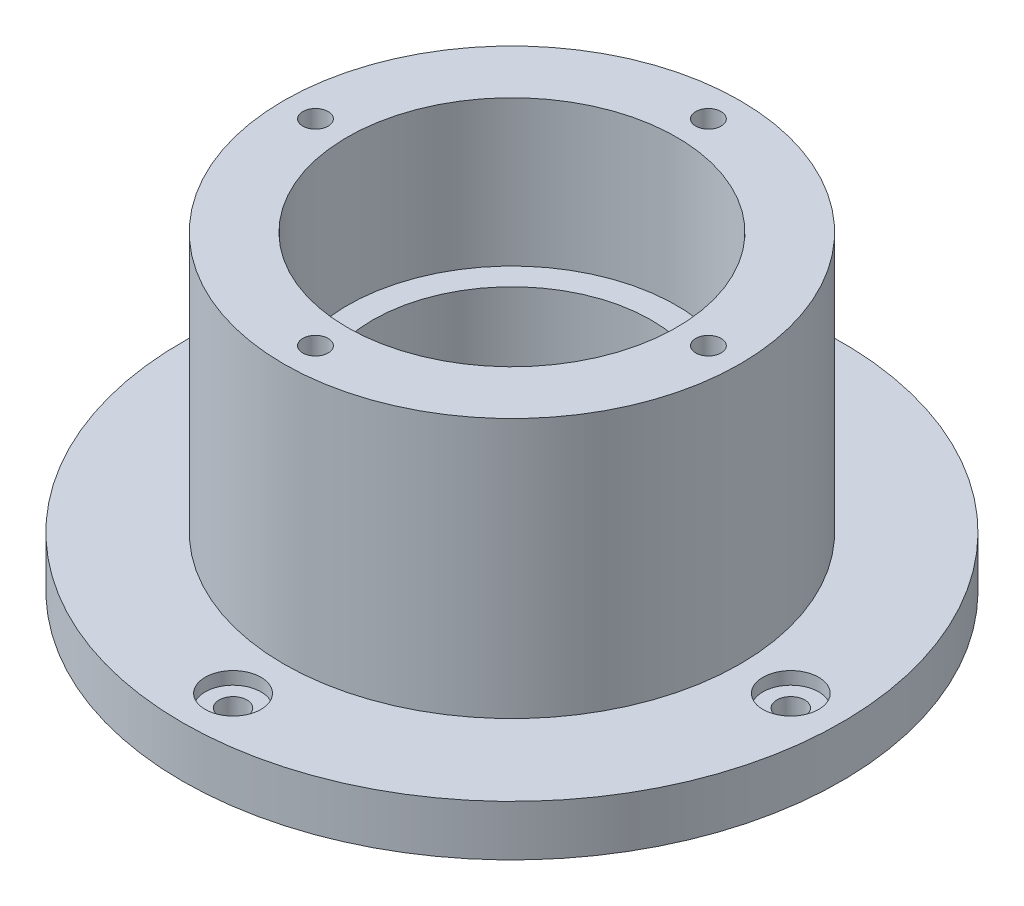
SolidWorks part; units mm, degrees
material "ABS"
ref_plane "Спереди" through (0, 0, 0) normal (0, 0, 1) x (1, 0, 0)
ref_plane "Сверху" through (0, 0, 0) normal (0, 1, 0) x (1, 0, 0)
ref_plane "Справа" through (0, 0, 0) normal (1, 0, 0) x (0, 0, -1)
sketch "Эскиз1" plane through (0, 0, 0) normal (0, 1, 0) x (1, 0, 0)
  circle A0 centre (0, 0) radius 26
  dimension "D1" = 52
extrude "Бобышка-Вытянуть1" add sketch "Эскиз1" along normal blind 4
sketch "Эскиз2" plane through (0, 4, 0) normal (0, 1, 0) x (1, 0, 0)
  circle A0 centre (0, 0) radius 18
  dimension "D1" = 36
extrude "Бобышка-Вытянуть2" add sketch "Эскиз2" along normal blind 20.5
sketch "Эскиз3" plane through (0, 24.5, 0) normal (0, 1, 0) x (1, 0, 0)
  circle A0 centre (0, 0) radius 13
  dimension "D1" = 26
extrude "Вырез-Вытянуть1" cut sketch "Эскиз3" along direction (0, 1, 0) on the side against the normal offset from surface (11.5 mm away) 13 up to face at (0, 0, 26)
sketch "Эскиз4" plane through (0, 4, 0) normal (0, 1, 0) x (1, 0, 0)
  circle A0 centre (0, 0) radius 22 construction
  circle A1 centre (-22, 0) radius 2.2
  circle A2 centre (0, 22) radius 2.2
  circle A3 centre (22, 0) radius 2.2
  circle A4 centre (0, -22) radius 2.2
  point P14 (0, 0)
  dimension "D1" = 44
  dimension "D2" = 4.4
extrude "Вырез-Вытянуть2" cut sketch "Эскиз4" against normal blind 1
sketch "Эскиз5" plane through (0, 4, 0) normal (0, 1, 0) x (1, 0, 0)
  circle A0 centre (-22, 0) radius 1.1
  circle A1 centre (0, 22) radius 1.1
  circle A2 centre (22, 0) radius 1.1
  circle A3 centre (0, -22) radius 1.1
  point P12 (0, 0)
  dimension "D1" = 2.2
extrude "Вырез-Вытянуть3" cut sketch "Эскиз5" against normal through all
sketch "Эскиз6" plane through (0, 13, 0) normal (0, 1, 0) x (1, 0, 0)
  circle A0 centre (0, 0) radius 11
  dimension "D1" = 22
extrude "Вырез-Вытянуть4" cut sketch "Эскиз6" against normal through all
sketch "Эскиз7" plane through (0, 24.5, 0) normal (0, 1, 0) x (1, 0, 0)
  circle A0 centre (0, 0) radius 15.5 construction
  circle A1 centre (-15.5, 0) radius 1
  circle A2 centre (0, 15.5) radius 1
  circle A3 centre (15.5, 0) radius 1
  circle A4 centre (0, -15.5) radius 1
  point P14 (0, 0)
  dimension "D1" = 31
  dimension "D2" = 2
extrude "Вырез-Вытянуть5" cut sketch "Эскиз7" against normal blind 5
